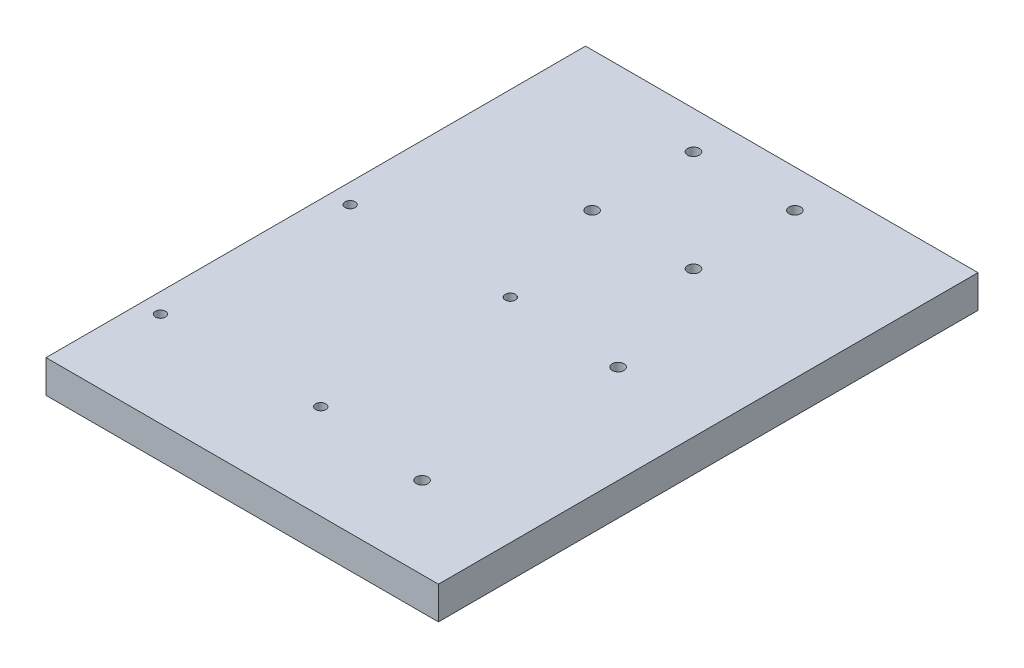
SolidWorks part; units mm, degrees
ref_plane "Front Plane" through (0, 0, 0) normal (0, 0, 1) x (1, 0, 0)
ref_plane "Top Plane" through (0, 0, 0) normal (0, 1, 0) x (1, 0, 0)
ref_plane "Right Plane" through (0, 0, 0) normal (1, 0, 0) x (0, 0, -1)
sketch "Sketch1" plane through (0, 0, 0) normal (0, 1, 0) x (1, 0, 0)
  line L1 (0, 0) -> (120, 0)
  line L2 (0, 0) -> (0, 165)
  line L3 (0, 165) -> (120, 165)
  line L4 (120, 0) -> (120, 165)
  dimension "D1" = 120
  dimension "D2" = 165
extrude "Base" add sketch "Sketch1" along normal blind 10
hole_wizard "Pi-MountHoles" positions "Sketch13" profile "Sketch14" counterbore size "M2.5" standard "ANSI Metric" end condition up to next
sketch "Sketch13" plane through (0, 0, 0) normal (0, -1, 0) x (-1, 0, 0)
  line L1 (0, 0) -> (-120, 0) construction
  line L2 (0, 165) -> (0, 0) construction
  point P0 (-6, 29)
  point P2 (-55, 29)
  point P4 (-55, 87)
  point P6 (-6, 87)
  dimension "D1" = 49
  dimension "D2" = 58
  dimension "D3" = 87
  dimension "D4" = 6
sketch "Sketch14" plane through (6, 0, -29) normal (1, 0, 0) x (0, 0, -1)
  line L0 (0, 0) -> (0, 10)
  line L1 (0, 10) -> (1.55, 10)
  line L3 (1.55, 10) -> (1.55, 2.1)
  line L4 (3, 2.1) -> (1.55, 2.1)
  line L5 (3, 2.1) -> (3, 0.025)
  line L6 (3, 0.025) -> (3.025, 0)
  line L7 (3.025, 0) -> (0, 0)
  line L8 (-3, 0.025) -> (-3.025, 0) construction
  line L11 (0, -6.35) -> (0, 107.95) construction
  dimension "Thru Hole Dia." = 3.1
  dimension "Thru Hole Depth" = 10
  dimension "C'Bore Dia." = 6
  dimension "C'Bore Depth" = 2.1
  dimension "Near C'Sink Dia." = 6.05
  dimension "Near C'Sink Angle" = 90
hole_wizard "Battery-MountHoles" positions "Sketch15" profile "Sketch16" counterbore size "M3" standard "ANSI Metric" end condition up to next
sketch "Sketch15" plane through (0, 0, 0) normal (0, -1, 0) x (-1, 0, 0)
  line L0 (0, 0) -> (-120, 0) construction
  circle A0 centre (-55, 87) radius 1.55 construction
  point P0 (-90, 25)
  point P2 (-90, 84.95)
  dimension "D1" = 59.95
  dimension "D2" = 25
  dimension "D3" = 35
sketch "Sketch16" plane through (90, 0, -25) normal (1, 0, 0) x (0, 0, -1)
  line L0 (0, 0) -> (0, 10)
  line L1 (0, 10) -> (1.8, 10)
  line L3 (1.8, 10) -> (1.8, 2.4)
  line L4 (3.5, 2.4) -> (1.8, 2.4)
  line L5 (3.5, 2.4) -> (3.5, 0.025)
  line L6 (3.5, 0.025) -> (3.525, 0)
  line L7 (3.525, 0) -> (0, 0)
  line L8 (-3.5, 0.025) -> (-3.525, 0) construction
  line L11 (0, -6.35) -> (0, 107.95) construction
  dimension "Thru Hole Dia." = 3.6
  dimension "Thru Hole Depth" = 10
  dimension "C'Bore Dia." = 7
  dimension "C'Bore Depth" = 2.4
  dimension "Near C'Sink Dia." = 7.05
  dimension "Near C'Sink Angle" = 90
hole_wizard "Stepper-MountHoles" positions "Sketch11" profile "Sketch12" counterbore size "M3" standard "ANSI Metric" end condition up to next
sketch "Sketch11" plane through (0, 0, 0) normal (0, -1, 0) x (-1, 0, 0)
  line L0 (-120, 165) -> (0, 165) construction
  circle A1 centre (-55, 87) radius 1.55 construction
  point P0 (-75.5, 153.5)
  point P2 (-44.5, 153.5)
  point P4 (-44.5, 122.5)
  point P6 (-75.5, 122.5)
  point P12 (-60, 165)
  point P17 (-82.42, 83)
  point P20 (0, 0)
  point P21 (0, 0)
  dimension "D4" = 35.5
  dimension "D1" = 31
  dimension "D2" = 31
  dimension "D3" = 15.5
sketch "Sketch12" plane through (75.5, 0, -153.5) normal (1, 0, 0) x (0, 0, -1)
  line L0 (0, 0) -> (0, 10)
  line L1 (0, 10) -> (1.8, 10)
  line L3 (1.8, 10) -> (1.8, 2.4)
  line L4 (3.5, 2.4) -> (1.8, 2.4)
  line L5 (3.5, 2.4) -> (3.5, 0.025)
  line L6 (3.5, 0.025) -> (3.525, 0)
  line L7 (3.525, 0) -> (0, 0)
  line L8 (-3.5, 0.025) -> (-3.525, 0) construction
  line L11 (0, -6.35) -> (0, 107.95) construction
  dimension "Thru Hole Dia." = 3.6
  dimension "Thru Hole Depth" = 10
  dimension "C'Bore Dia." = 7
  dimension "C'Bore Depth" = 2.4
  dimension "Near C'Sink Dia." = 7.05
  dimension "Near C'Sink Angle" = 90
